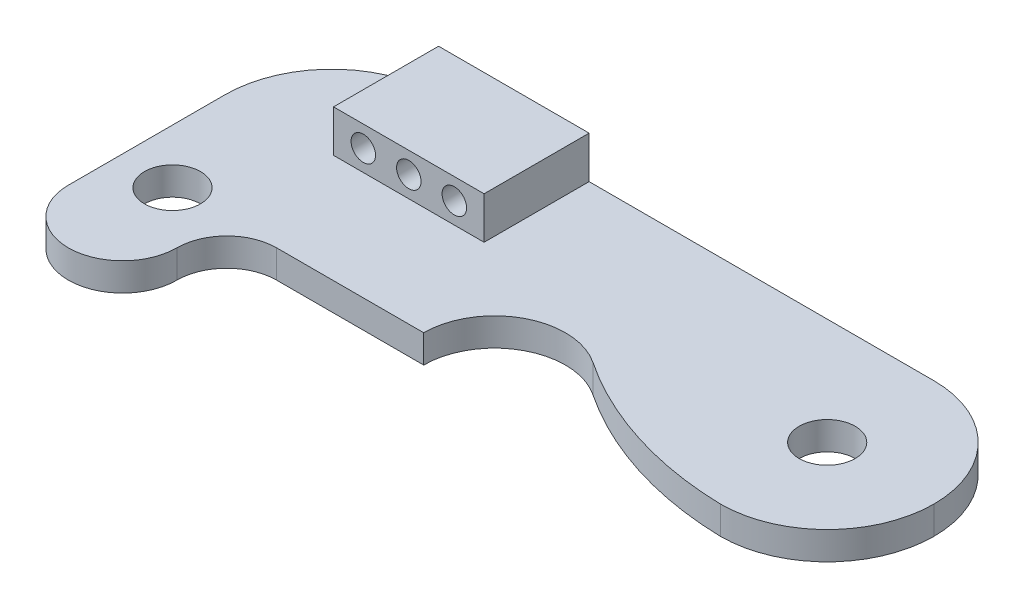
SolidWorks part; units mm, degrees
ref_plane "Front Plane" through (0, 0, 0) normal (0, 0, 1) x (1, 0, 0)
ref_plane "Top Plane" through (0, 0, 0) normal (0, 1, 0) x (1, 0, 0)
ref_plane "Right Plane" through (0, 0, 0) normal (1, 0, 0) x (0, 0, -1)
sketch "Sketch1" plane through (0, 0, 0) normal (0, 1, 0) x (1, 0, 0)
  line L15 (32.8531, -176.6025) -> (73.3531, -176.6025)
  line L17 (41.9031, -188.8025) -> (73.3531, -188.8025)
  line L21 (32.8531, -176.6025) -> (32.8531, -191.6525)
  line L22 (32.8531, -191.6525) -> (39.0531, -191.6525) construction
  line L24 (41.9031, -191.6525) -> (41.9031, -188.8025) construction
  line L28 (73.3531, -176.6025) -> (73.3531, -188.8025)
  arc A14 (41.9031, -188.8025) -> (39.0531, -191.6525) centre (41.9031, -191.6525) ccw
  arc A16 (32.8531, -191.6525) -> (39.0531, -191.6525) centre (35.9531, -191.6525) ccw
  point P8 (73.3531, -182.7025)
  dimension "D1" = 3.1
  dimension "D4" = 2.85
  dimension "D5" = 40.5
  dimension "D6" = 12.2
  dimension "D12" = 90
  dimension "D8" = 6.2
extrude "Boss-Extrude1" add sketch "Sketch1" along normal blind 1.6 contours L21 A16 A14 L17 L15 region at (51.9959, 0, 183.2694)
sketch "Sketch4" plane through (0, 1.6, 0) normal (0, 1, 0) x (1, 0, 0)
  line L0 (32.8531, -176.6025) -> (32.8531, -191.6525) construction
  line L1 (73.3531, -176.6025) -> (73.3531, -188.8025) construction
  line L2 (41.9031, -188.8025) -> (73.3531, -188.8025) construction
  line L3 (73.3531, -176.6025) -> (73.3531, -188.8025) construction
  line L4 (50.3031, -188.8025) -> (58.4031, -188.8025)
  line L6 (32.8531, -176.6025) -> (73.3531, -176.6025) construction
  circle A0 centre (67.2531, -182.7025) radius 1.6
  arc A1 (58.4031, -188.8025) -> (50.3031, -188.8025) centre (54.3531, -188.8025) ccw
  circle A2 centre (35.9531, -188.8025) radius 1.6
  dimension "D1" = 3.2
  dimension "D4" = 8.1
  dimension "D6" = 3.2
  dimension "D2" = 6.1
  dimension "D3" = 6.1
  dimension "D5" = 19
  dimension "D7" = 3.1
  dimension "D8" = 12.2
extrude "Cut-Extrude2" cut sketch "Sketch4" against normal through all
fillet "Fillet2" radius 6.1 3 edges at (73.3531, 0.8, 176.6025) (73.3531, 0.8, 188.8025) (32.8531, 0.8, 176.6025)
sketch "Sketch2" plane through (0, 1.6, 0) normal (0, 1, 0) x (1, 0, 0)
  line L0 (32.8531, -182.7025) -> (32.8531, -191.6525) construction
  line L1 (38.9531, -176.6025) -> (47.5531, -176.6025)
  line L2 (38.9531, -176.6025) -> (38.9531, -182.6025)
  line L3 (38.9531, -182.6025) -> (47.5531, -182.6025)
  line L4 (47.5531, -176.6025) -> (47.5531, -182.6025)
  dimension "D1" = 6
  dimension "D2" = 8.6
  dimension "D3" = 6.1
extrude "Boss-Extrude2" add sketch "Sketch2" along normal blind 2.4
sketch "Sketch3" plane through (0, 0, 176.6025) normal (0, 0, -1) x (-1, 0, 0)
  line L0 (-47.5531, 4) -> (-38.9531, 4) construction
  line L1 (-38.9531, 4) -> (-38.9531, 1.6) construction
  line L2 (-47.5531, 4) -> (-47.5531, 1.6) construction
  circle A0 centre (-45.8531, 2.8) radius 0.7
  circle A1 centre (-40.6531, 2.8) radius 0.7
  circle A2 centre (-43.2531, 2.8) radius 0.7
  dimension "D5" = 1.4
  dimension "D6" = 1.4
  dimension "D7" = 2.6
  dimension "D10" = 1.4
  dimension "D1" = 1.2
  dimension "D2" = 1.2
  dimension "D3" = 1.7
  dimension "D4" = 1.7
  dimension "D8" = 2.6
  dimension "D9" = 1.2
extrude "Cut-Extrude1" cut sketch "Sketch3" against normal up to next
fillet "Fillet1" radius 20 1 edges at (58.4031, 0.8, 188.8025)
